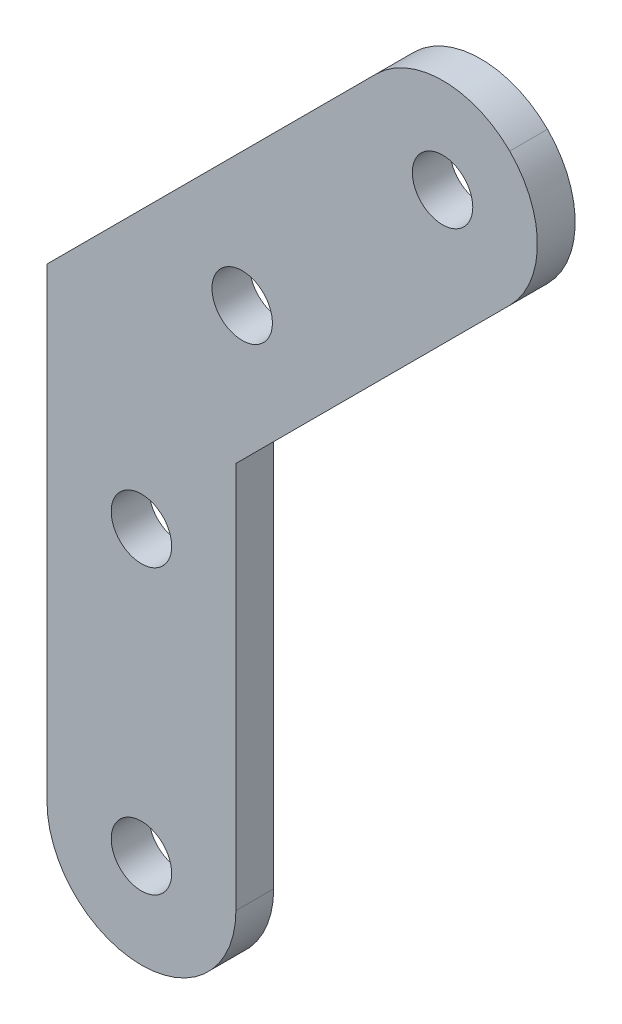
SolidWorks part; units mm, degrees
material "5052-O"
ref_plane "正面" through (0, 0, 0) normal (0, 0, 1) x (1, 0, 0)
ref_plane "平面" through (0, 0, 0) normal (0, 1, 0) x (1, 0, 0)
ref_plane "右側面" through (0, 0, 0) normal (1, 0, 0) x (0, 0, -1)
sketch "ｽｹｯﾁ1" plane through (0, 0, 0) normal (0, 0, 1) x (1, 0, 0)
  line L0 (-3.8279, 2.447) -> (-3.8279, -19.7772)
  line L5 (-3.8279, -19.7772) -> (6.1721, -19.7772)
  line L6 (6.1721, -19.7772) -> (6.1721, 5.7228)
  line L7 (6.1721, 5.7228) -> (24.2034, 23.754)
  line L8 (24.2034, 23.754) -> (17.1323, 30.8251)
  line L9 (17.1323, 30.8251) -> (-3.8279, 9.8649)
  line L10 (-3.8279, 9.8649) -> (-3.8279, 2.447)
  dimension "D1" = 25.5
  dimension "D2" = 10
  dimension "D3" = 10
  dimension "D4" = 360
  dimension "D5" = 135
  dimension "D6" = 135
  dimension "D7" = 25.5
  dimension "D8" = 90
  dimension "D9" = 180
  dimension "D10" = 90
extrude "ﾎﾞｽ - 押し出し1" add sketch "ｽｹｯﾁ1" along normal mid plane 2
fillet "ﾌｨﾚｯﾄ1" radius 5 4 edges at (17.1323, 30.8251, 0) (-3.8279, -19.7772, 0) (6.1721, -19.7772, 0) (24.2034, 23.754, 0)
sketch "ｽｹｯﾁ2" plane through (0, 0, 1) normal (0, 0, 1) x (1, 0, 0)
  line L0 (6.1721, -14.7772) -> (6.1721, 5.7228) construction
  line L1 (6.1721, 5.7228) -> (-3.8279, 5.7228)
  line L2 (-3.8279, 9.8649) -> (-3.8279, -14.7772) construction
  line L3 (6.1721, 5.7228) -> (-0.9401, 12.7527)
  line L5 (13.5968, 27.2896) -> (-3.8279, 9.8649) construction
  line L6 (6.1721, 5.7228) -> (20.6678, 20.2185) construction
  circle A0 centre (1.1721, 0.2228) radius 1.6
  circle A1 centre (1.1721, -14.7772) radius 1.6
  circle A2 centre (6.5052, 13.1269) radius 1.6
  circle A3 centre (17.1118, 23.7335) radius 1.6
  dimension "D1" = 3.2
  dimension "D2" = 5
  dimension "D3" = 5.5
  dimension "D5" = 3.2
  dimension "D6" = 5
  dimension "D7" = 5.5
  dimension "D4" = 2
  dimension "D8" = 2
extrude "ｶｯﾄ - 押し出し1" cut sketch "ｽｹｯﾁ2" against normal through all contours A3 | A2 | A0 | A1
